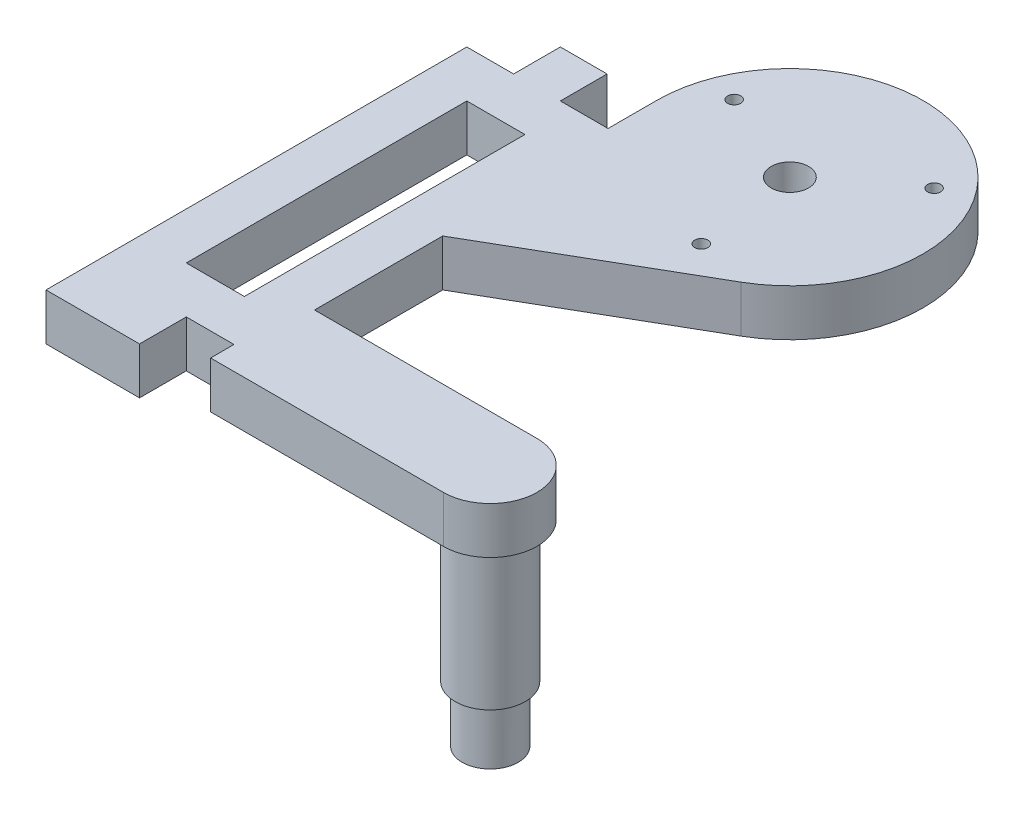
SolidWorks part; units mm, degrees
ref_plane "Front Plane" through (0, 0, 0) normal (0, 0, 1) x (1, 0, 0)
ref_plane "Top Plane" through (0, 0, 0) normal (0, 1, 0) x (1, 0, 0)
ref_plane "Right Plane" through (0, 0, 0) normal (1, 0, 0) x (0, 0, -1)
sketch "Sketch1" plane through (0, 0, 0) normal (0, 1, 0) x (1, 0, 0)
  line L1 (0, 0) -> (45, 0)
  line L2 (0, 0) -> (0, 12)
  line L3 (0, 12) -> (45, 12)
  line L5 (0, 0) -> (15, 0)
  line L6 (0, 0) -> (0, -5)
  line L7 (0, -5) -> (15, -5)
  line L8 (15, 0) -> (15, -5)
  line L9 (0, 12) -> (24, 12)
  line L10 (0, 12) -> (0, 55.0692)
  line L11 (0, 55.0692) -> (24, 55.0692)
  line L12 (24, 12) -> (24, 55.0692)
  circle A0 centre (45, 6) radius 3
  arc A1 (45, 0) -> (45, 12) centre (45, 6) ccw
  circle A6 centre (12, 53.0692) radius 0.7
  circle A7 centre (21.5263, 36.5692) radius 0.7
  circle A8 centre (2.4737, 36.5692) radius 0.7
  circle A11 centre (12, 42.0692) radius 2
  dimension "D4" = 45
  dimension "D3" = 6
  dimension "D11" = 1.4
  dimension "D1" = 5
  dimension "D2" = 15
  dimension "D5" = 6
  dimension "D13" = 3
sketch "Sketch2" plane through (0, 0, 0) normal (0, 1, 0) x (1, 0, 0)
  line L0 (15.1, 45.212) -> (15.1, 40)
  line L1 (0, 0) -> (15, 0)
  line L5 (0, 0) -> (15.1, 0)
  line L6 (0, 0) -> (0, 40)
  line L7 (0, 40) -> (16.2133, 40)
  line L8 (16.2133, 7.5) -> (16.2133, 40)
  line L9 (10, 40) -> (5, 40)
  line L10 (10, 40) -> (10, 45)
  line L11 (10, 45) -> (5, 45)
  line L12 (5, 40) -> (5, 45)
  line L17 (14.5855, 20.2678) -> (36.4451, 32.8884)
  line L18 (36.4451, 32.8884) -> (16.2133, 21.2076)
  line L19 (29.3301, 45.212) -> (38.057, 51.9084) construction
  line L20 (16.2133, 7.5) -> (40, 7.5)
  line L21 (15.1, 0) -> (15.1, -2.5)
  line L22 (15.1, -2.5) -> (40, -2.5)
  line L25 (5, 35) -> (11.2133, 35)
  line L26 (5, 35) -> (5, 5)
  line L27 (5, 5) -> (11.2133, 5)
  line L28 (11.2133, 35) -> (11.2133, 5)
  line L29 (0, 0) -> (10, 0)
  line L30 (0, 0) -> (0, -5)
  line L31 (0, -5) -> (10, -5)
  line L32 (10, 0) -> (10, -5)
  circle A10 centre (29.3301, 45.212) radius 14.2301
  circle A11 centre (29.3301, 45.212) radius 2
  circle A12 centre (40, 2.5) radius 39.7 construction
  circle A13 centre (29.3301, 45.212) radius 4.3246 construction
  arc A14 (40, -2.5) -> (40, 7.5) centre (40, 2.5) ccw
  circle A15 centre (38.057, 51.9084) radius 0.7
  circle A18 centre (30.7659, 34.3061) radius 0.7
  circle A19 centre (19.1674, 49.4216) radius 0.7
  point P39 (5, 42.5)
  dimension "D5" = 79.4
  dimension "D6" = 40
  dimension "D7" = 5.1
  dimension "D8" = 2.5
  dimension "D9" = 60
  dimension "D10" = 5
  dimension "D14" = 52.5
  dimension "D1" = 40
  dimension "D2" = 5
  dimension "D3" = 5
  dimension "D4" = 10
  dimension "D11" = 5
  dimension "D12" = 11
  dimension "D13" = 5
  dimension "D16" = 5
  dimension "D17" = 5
  dimension "D18" = 5
  dimension "D19" = 5
  dimension "D20" = 5.1
  dimension "D21" = 5
  dimension "D15" = 3
extrude "Boss-Extrude1" add sketch "Sketch2" along normal blind 5 contours A10 L7 L8 A15 A11 | L22 A14 L20 L8 A10 L7 L6 L1 L5 L21 | L12 L7 L10 L11 | L1 | L7 A10 L8 | A10 L8 L18 L17 | A10 L0 L7 region at (15.3948, 0, -41.2938) region at (29.3301, 0, -59.0396) region at (15.5944, 0, -39.381) region at (16.1716, 0, -39.8976) region at (7.5, 0, -42.5) region at (21.2648, 0, -29.3097) region at (5, 0, 2.5)
sketch "Sketch3" plane through (0, 5, 0) normal (0, 1, 0) x (1, 0, 0)
  circle A0 centre (40, 2.5) radius 3.75
extrude "Boss-Extrude2" add sketch "Sketch3" against normal blind 20
sketch "Sketch4" plane through (0, -15, 0) normal (0, -1, 0) x (-1, 0, 0)
  circle A0 centre (-40, 2.5) radius 3
  circle A1 centre (-40, 2.5) radius 1.75
extrude "Boss-Extrude3" add sketch "Sketch4" along normal blind 6
